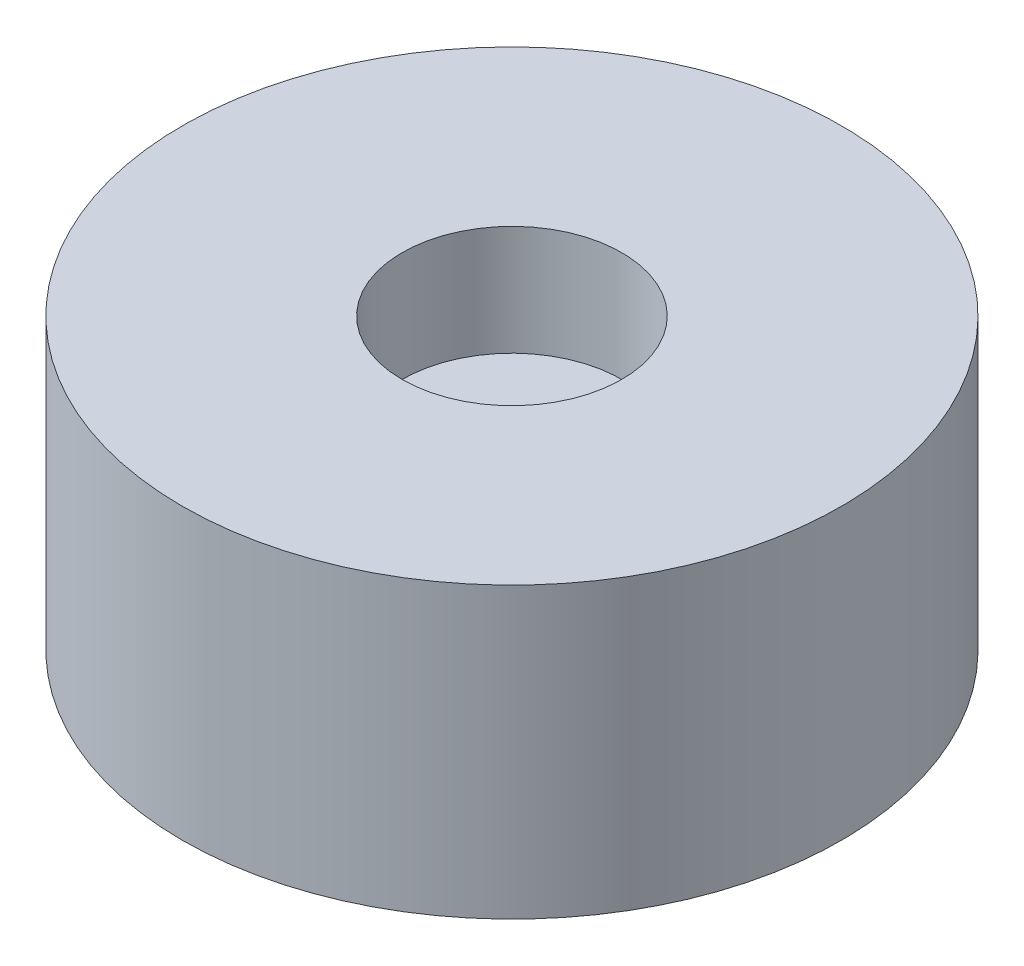
SolidWorks part; units mm, degrees
ref_plane "Front Plane" through (0, 0, 0) normal (0, 0, 1) x (1, 0, 0)
ref_plane "Top Plane" through (0, 0, 0) normal (0, 1, 0) x (1, 0, 0)
ref_plane "Right Plane" through (0, 0, 0) normal (1, 0, 0) x (0, 0, -1)
sketch "Sketch1" plane through (0, 0, 0) normal (0, 1, 0) x (1, 0, 0)
  circle A0 centre (0, 0) radius 9
  dimension "D1" = 18
extrude "Boss-Extrude1" add sketch "Sketch1" along normal blind 7.9
sketch "Sketch2" plane through (0, 7.9, 0) normal (0, 1, 0) x (1, 0, 0)
  circle A0 centre (0, 0) radius 3
  dimension "D1" = 6
extrude "Cut-Extrude1" cut sketch "Sketch2" against normal blind 3
sketch "Sketch3" plane through (0, 0, 0) normal (0, -1, 0) x (1, 0, 0)
  circle A0 centre (0, 0) radius 3.5
  dimension "D1" = 7
extrude "Boss-Extrude2" add sketch "Sketch3" along normal blind 1.6
hole_wizard "Tapped Hole for M2.5x0.45 Helicoil1" positions "Sketch4" profile "Sketch5" tap size "M2.5x0.45" standard "Helicoil® Metric"
sketch "Sketch4" plane through (0, -1.6, 0) normal (0, -1, 0) x (-1, 0, 0)
  point P0 (0, 0)
sketch "Sketch5" plane through (0, -1.6, 0) normal (1, 0, 0) x (0, 0, -1)
  line L0 (0, 0) -> (0, 4.7661)
  line L1 (0, 4.7661) -> (1.275, 4)
  line L2 (1.275, 4) -> (1.275, 0.3225)
  line L3 (1.275, 0.3225) -> (1.5975, 0)
  line L5 (1.5975, 0) -> (0, 0)
  line L6 (-1.275, 0.3225) -> (-1.5975, 0) construction
  line L10 (0, 4.7661) -> (-1.275, 4) construction
  line L11 (0, -6.35) -> (0, 107.95) construction
  dimension "Tap Drill Dia." = 2.55
  dimension "Tap Drill Depth" = 4
  dimension "Near C'Sink Dia." = 3.195
  dimension "Near C'Sink Angle" = 90
  dimension "Drill Angle" = 118
cosmetic thread "Hole Thread2" parameters "D1"=3, "D2"=3.145
